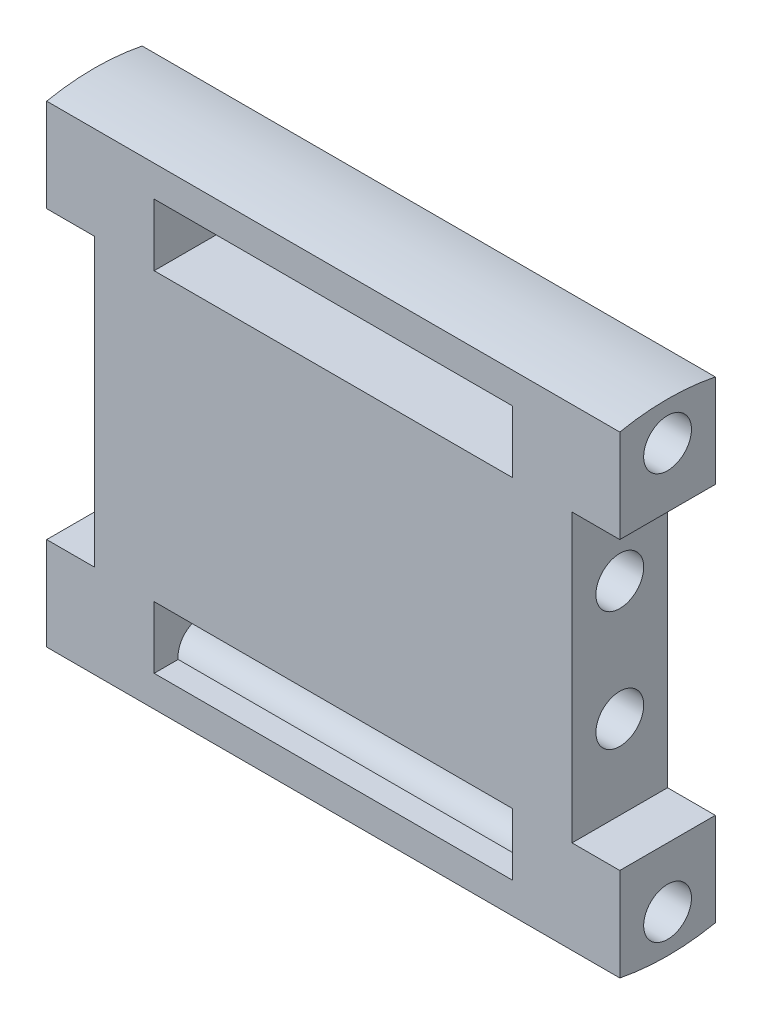
SolidWorks part; units mm, degrees
ref_plane "Front Plane" through (0, 0, 0) normal (0, 0, 1) x (1, 0, 0)
ref_plane "Top Plane" through (0, 0, 0) normal (0, 1, 0) x (1, 0, 0)
ref_plane "Right Plane" through (0, 0, 0) normal (1, 0, 0) x (0, 0, -1)
sketch "Sketch1" plane through (0, 0, 0) normal (1, 0, 0) x (0, 0, -1)
  line L0 (-10, 49.5) -> (-10, -49.5)
  line L1 (10, 49.5) -> (10, -49.5)
  line L2 (-10, 0) -> (10, 0) construction
  circle A0 centre (0, 0) radius 50.5 construction
  arc A1 (-10, 49.5) -> (10, 49.5) centre (0, 0) cw
  arc A2 (-10, -49.5) -> (10, -49.5) centre (0, 0) ccw
  point P10 (0, 0)
  dimension "D1" = 101
  dimension "D2" = 20
extrude "Boss-Extrude1" add sketch "Sketch1" along normal blind 125
sketch "Sketch2" plane through (0, 0, 0) normal (1, 0, 0) x (0, 0, -1)
  circle A0 centre (0, 0) radius 50.5
  arc A1 (10, 49.5) -> (-10, 49.5) centre (0, 0) ccw construction
extrude "Boss-Extrude2" add sketch "Sketch2" along normal blind 5
sketch "Sketch3" plane through (0, 0, -10) normal (0, 0, -1) x (-1, 0, 0)
  line L0 (-5, -49.5) -> (-5, 49.5) construction
  line L1 (-15, 30) -> (-5, 30)
  line L2 (-15, 30) -> (-15, -30)
  line L3 (-15, -30) -> (-5, -30)
  line L4 (-5, 30) -> (-5, -30)
  line L5 (-65, 49.5) -> (-65, -49.5) construction
  line L6 (-125, 49.5) -> (-5, 49.5) construction
  line L7 (-125, -49.5) -> (-5, -49.5) construction
  line L8 (-125, 30) -> (-125, -30)
  line L9 (-115, -30) -> (-125, -30)
  line L10 (-115, 30) -> (-115, -30)
  line L11 (-115, 30) -> (-125, 30)
  point P6 (-5, 0)
  dimension "D1" = 10
  dimension "D2" = 60
extrude "Cut-Extrude1" cut sketch "Sketch3" against normal through all
sketch "Sketch7" plane through (0, 0, 0) normal (-1, 0, 0) x (0, 0, 1)
  line L0 (0, 26) -> (0, -26) construction
  line L1 (-31, 26) -> (31, 26)
  line L2 (-31, 26) -> (-31, -26)
  line L3 (-31, -26) -> (31, -26)
  line L4 (31, 26) -> (31, -26)
  point P6 (0, 0)
  dimension "D1" = 52
  dimension "D2" = 62
extrude "Cut-Extrude3" cut sketch "Sketch7" against normal up to surface (5 mm away) up to face at (5, 0, 0)
sketch "Sketch8" plane through (125, 0, 0) normal (1, 0, 0) x (0, 0, -1)
  line L0 (32.6497, -34.5) -> (36.8782, -34.5) construction
  line L1 (-29.3503, 34.5) -> (32.6497, 34.5)
  line L2 (-29.3503, 34.5) -> (-29.3503, -34.5)
  line L3 (-29.3503, -34.5) -> (32.6497, -34.5)
  line L4 (32.6497, 34.5) -> (32.6497, -34.5)
  line L5 (50.5, 0) -> (32.6497, 0) construction
  line L6 (32.6497, -34.5) -> (34.7117, -36.6789) construction
  circle A0 centre (0, 0) radius 50.5
  arc A1 (10, 49.5) -> (-10, 49.5) centre (0, 0) ccw construction
  point P6 (0, 0)
  dimension "D1" = 62
  dimension "D2" = 69
  dimension "D3" = 3
extrude "Boss-Extrude4" add sketch "Sketch8" along normal blind 140
sketch "Sketch22" plane through (125, 0, 0) normal (-1, 0, 0) x (0, 0, 1)
  line L0 (-50.5, 0) -> (-40.5, 0) construction
  line L1 (-50.5, 12.5) -> (-40.5, 12.5)
  line L2 (-50.5, 12.5) -> (-50.5, -12.5)
  line L3 (-50.5, -12.5) -> (-40.5, -12.5)
  line L4 (-40.5, 12.5) -> (-40.5, -12.5)
  arc A0 (-10, 49.5) -> (-10, -49.5) centre (0, 0) ccw construction
  point P10 (-50.5, 0)
  dimension "D1" = 10
  dimension "D2" = 25
extrude "Cut-Extrude14" cut sketch "Sketch22" against normal up to next
sketch "Sketch10" plane through (265, 0, 0) normal (1, 0, 0) x (0, 0, -1)
  line L0 (-10, 49.5) -> (-10, -49.5)
  line L1 (10, 49.5) -> (10, -49.5)
  line L2 (-10, 0) -> (10, 0) construction
  line L4 (-10, 49.5) -> (-10, 34.5) construction
  arc A0 (-10, 49.5) -> (10, 49.5) centre (0, 0) cw
  circle A1 centre (0, 0) radius 50.5 construction
  arc A2 (-10, -49.5) -> (10, -49.5) centre (0, 0) ccw
  point P13 (0, 0)
extrude "Boss-Extrude5" add sketch "Sketch10" along normal blind 125
sketch "Sketch11" plane through (0, 0, 0) normal (0, 0, 1) x (1, 0, 0)
  line L0 (390, 0) -> (0, 0) construction
  line L1 (2.75, 0) -> (-2.75, 0) construction
  line L2 (0, 26) -> (0, -26) construction
  line L3 (390, 49.5) -> (390, 50.5) construction
  line L4 (195, -30) -> (195, 30) construction
  line L5 (265, -30) -> (125, -30)
  line L6 (265, -30) -> (265, 30)
  line L7 (265, 30) -> (125, 30)
  line L8 (125, -30) -> (125, 30)
  line L9 (265, 49.5) -> (265, 34.5) construction
  point P15 (195, 0)
  dimension "D1" = 60
extrude "Cut-Extrude5" cut sketch "Sketch11" along normal through all
chamfer "Chamfer2" distance 5 angle 20 2 edges at (195, -30, 29.3503) (195, 30, 29.3503) first distance on face at (195, -30, 34.9868) first distance on face at (195, 30, 34.9868)
sketch "Sketch9" plane through (0, 0, 0) normal (1, 0, 0) x (0, 0, -1)
  line L0 (0, -34.5) -> (0, -50.5) construction
  line L2 (-50.5, 0) -> (50.5, 0) construction
  line L3 (-29.3503, -34.5) -> (-10, -34.5) construction
  circle A1 centre (0, -42.5) radius 5
  circle A2 centre (0, 0) radius 50.5 construction
  circle A3 centre (0, 42.5) radius 5
  point P11 (0, -42.5)
  dimension "D1" = 10
extrude "Cut-Extrude4" cut sketch "Sketch9" along normal through all
sketch "Sketch12" plane through (0, 0, -10) normal (0, 0, -1) x (-1, 0, 0)
  line L0 (-265, -34.5) -> (-265, 34.5) construction
  line L1 (-265, 30) -> (-275, 30)
  line L2 (-265, 30) -> (-265, -30)
  line L3 (-265, -30) -> (-275, -30)
  line L4 (-275, 30) -> (-275, -30)
  line L5 (-125, -30) -> (-115, -30) construction
  line L6 (-115, 30) -> (-125, 30) construction
  line L7 (-380, 30) -> (-380, -30)
  line L9 (-327.5, -49.5) -> (-327.5, 49.5) construction
  line L10 (-390, 49.5) -> (-265, 49.5) construction
  line L11 (-390, -49.5) -> (-265, -49.5) construction
  line L12 (-390, -30) -> (-380, -30)
  line L13 (-390, 30) -> (-390, -30)
  line L14 (-390, 30) -> (-380, 30)
  point P19 (-327.5, 49.5)
  point P23 (-327.5, -49.5)
extrude "Cut-Extrude6" cut sketch "Sketch12" against normal up to next
sketch "Sketch14" plane through (0, 0, 0) normal (1, 0, 0) x (0, 0, -1)
  line L0 (0, 12.5) -> (0, -12.5) construction
  circle A0 centre (0, 12.5) radius 5
  circle A1 centre (0, -12.5) radius 5
  point P2 (0, 0)
  dimension "D1" = 10
  dimension "D2" = 12.5
extrude "Cut-Extrude8" cut sketch "Sketch14" along normal through all
sketch "Sketch15" plane through (0, 0, 10) normal (0, 0, 1) x (1, 0, 0)
  line L0 (65, 49.5) -> (65, -49.5) construction
  line L1 (27.5, 43) -> (102.5, 43)
  line L2 (27.5, 43) -> (27.5, 30)
  line L3 (27.5, 30) -> (102.5, 30)
  line L4 (102.5, 43) -> (102.5, 30)
  line L5 (125, 49.5) -> (5, 49.5) construction
  line L6 (125, -49.5) -> (5, -49.5) construction
  line L7 (15, 30) -> (27.5, 30) construction
  line L8 (15, 0) -> (115, 0) construction
  line L9 (15, 30) -> (15, -30) construction
  line L10 (115, -30) -> (115, 30) construction
  line L11 (27.5, -30) -> (102.5, -30)
  line L12 (102.5, -43) -> (102.5, -30)
  line L13 (27.5, -43) -> (102.5, -43)
  line L14 (27.5, -43) -> (27.5, -30)
  point P10 (65, 43)
  dimension "D1" = 13
  dimension "D2" = 75
extrude "Cut-Extrude9" cut sketch "Sketch15" against normal through all
sketch "Sketch17" plane through (390, 0, 0) normal (1, 0, 0) x (0, 0, -1)
  circle A0 centre (0, 0) radius 50.5
  arc A1 (-10, -49.5) -> (10, -49.5) centre (0, 0) ccw construction
  circle A2 centre (0, 42.5) radius 5
  circle A3 centre (0, -42.5) radius 5
  circle A4 centre (0, -42.5) radius 5 construction
  circle A5 centre (0, 42.5) radius 5 construction
extrude "Boss-Extrude6" add sketch "Sketch17" along normal blind 5
sketch "Sketch18" plane through (395, 0, 0) normal (1, 0, 0) x (0, 0, -1)
  line L0 (0, 0) -> (-25, 0) construction
  line L5 (-25, 17.5) -> (23, 17.5)
  line L6 (-25, 17.5) -> (-25, -17.5)
  line L7 (-25, -17.5) -> (23, -17.5)
  line L8 (23, 17.5) -> (23, -17.5)
  dimension "D1" = 23
  dimension "D2" = 35
  dimension "D3" = 25
extrude "Cut-Extrude11" cut sketch "Sketch18" against normal up to next
sketch "Sketch19" plane through (395, 0, 0) normal (1, 0, 0) x (0, 0, -1)
  line L0 (-25, 17.5) -> (-25, -17.5) construction
  line L1 (-45, 10) -> (-25, 10)
  line L2 (-45, 10) -> (-45, -10)
  line L3 (-45, -10) -> (-25, -10)
  line L4 (-25, 10) -> (-25, -10)
  line L5 (-25, 0) -> (0, 0) construction
  dimension "D1" = 20
  dimension "D2" = 20
extrude "Boss-Extrude7" add sketch "Sketch19" along normal blind 26
sketch "Sketch20" plane through (0, 0, 25) normal (0, 0, -1) x (-1, 0, 0)
  line L0 (-421, 0) -> (-418, 0) construction
  line L1 (-418, -6.25) -> (-394.5, -6.25)
  line L2 (-418, -6.25) -> (-418, 6.25)
  line L3 (-418, 6.25) -> (-394.5, 6.25)
  line L4 (-394.5, -6.25) -> (-394.5, 6.25)
  line L5 (-421, -10) -> (-421, 10) construction
  dimension "D1" = 12.5
  dimension "D2" = 23.5
  dimension "D3" = 3
extrude "Cut-Extrude12" cut sketch "Sketch20" against normal blind 16
chamfer "Chamfer1" distance 4 angle 45 6 edges at (421, 10, 35) (421, 0, 45) (421, -10, 35) (395, 10, 35) (395, 0, 45) (395, -10, 35)
sketch "Sketch24" plane through (0, 0, 0) normal (-1, 0, 0) x (0, 0, 1)
  line L0 (0, 50.5) -> (0, 26) construction
  line L1 (31, 26) -> (-31, 26) construction
  line L2 (0, 26) -> (0, 37) construction
  line L3 (0, 37) -> (-34.3693, 37) construction
  line L4 (0, 0) -> (-50.5, 0) construction
  circle A0 centre (-17, 37) radius 6
  circle A1 centre (0, 0) radius 50.5 construction
  circle A2 centre (17, 37) radius 6
  circle A3 centre (17, -37) radius 6
  circle A4 centre (-17, -37) radius 6
  dimension "D2" = 12
  dimension "D1" = 17
  dimension "D3" = 11
extrude "Cut-Extrude16" cut sketch "Sketch24" against normal up to surface (5 mm away) up to face at (5, 0, 0)
sketch "Sketch21" plane through (394.5, 0, 0) normal (1, 0, 0) x (0, 0, -1)
  line L0 (-41, 0) -> (-39, 0) construction
  line L1 (-39, -3.5) -> (-32, -3.5)
  line L2 (-39, -3.5) -> (-39, 3.5)
  line L3 (-39, 3.5) -> (-32, 3.5)
  line L4 (-32, -3.5) -> (-32, 3.5)
  line L5 (-41, -6.25) -> (-41, 6.25) construction
  dimension "D1" = 2
  dimension "D2" = 7
  dimension "D3" = 7
extrude "Cut-Extrude13" cut sketch "Sketch21" against normal up to next
sketch "Sketch23" plane through (0, 0, 25) normal (0, 0, -1) x (-1, 0, 0)
  line L0 (-394.5, -6.25) -> (-394.5, 6.25) construction
  line L1 (-394.5, -2.5) -> (-393, -2.5)
  line L2 (-394.5, -2.5) -> (-394.5, 2.5)
  line L3 (-394.5, 2.5) -> (-393, 2.5)
  line L4 (-393, -2.5) -> (-393, 2.5)
  point P7 (-394.5, 0)
  point P8 (-394.5, 0)
  dimension "D1" = 5
  dimension "D2" = 1.5
extrude "Cut-Extrude15" cut sketch "Sketch23" against normal up to next
sketch "Sketch16" plane through (421, 0, 0) normal (1, 0, 0) x (0, 0, -1)
  line L1 (-92.8441, 90.798) -> (129.0663, 90.798)
  line L2 (-92.8441, 90.798) -> (-92.8441, -111.538)
  line L3 (-92.8441, -111.538) -> (129.0663, -111.538)
  line L4 (129.0663, 90.798) -> (129.0663, -111.538)
extrude "Cut-Extrude10" cut sketch "Sketch16" against normal up to surface (296 mm away) up to face at (125, 35.5278, 25.9145)
sketch "Sketch25" plane through (0, 0, 0) normal (-1, 0, 0) x (0, 0, 1)
  line L1 (-67.6025, 56.664) -> (67.6025, 56.664)
  line L2 (-67.6025, 56.664) -> (-67.6025, -56.664)
  line L3 (-67.6025, -56.664) -> (67.6025, -56.664)
  line L4 (67.6025, 56.664) -> (67.6025, -56.664)
  line L5 (-67.6025, 56.664) -> (67.6025, -56.664) construction
  line L6 (-67.6025, -56.664) -> (67.6025, 56.664) construction
  point P0 (0, 0)
extrude "Cut-Extrude17" cut sketch "Sketch25" against normal up to surface (5 mm away) up to face at (5, -37, -23)
